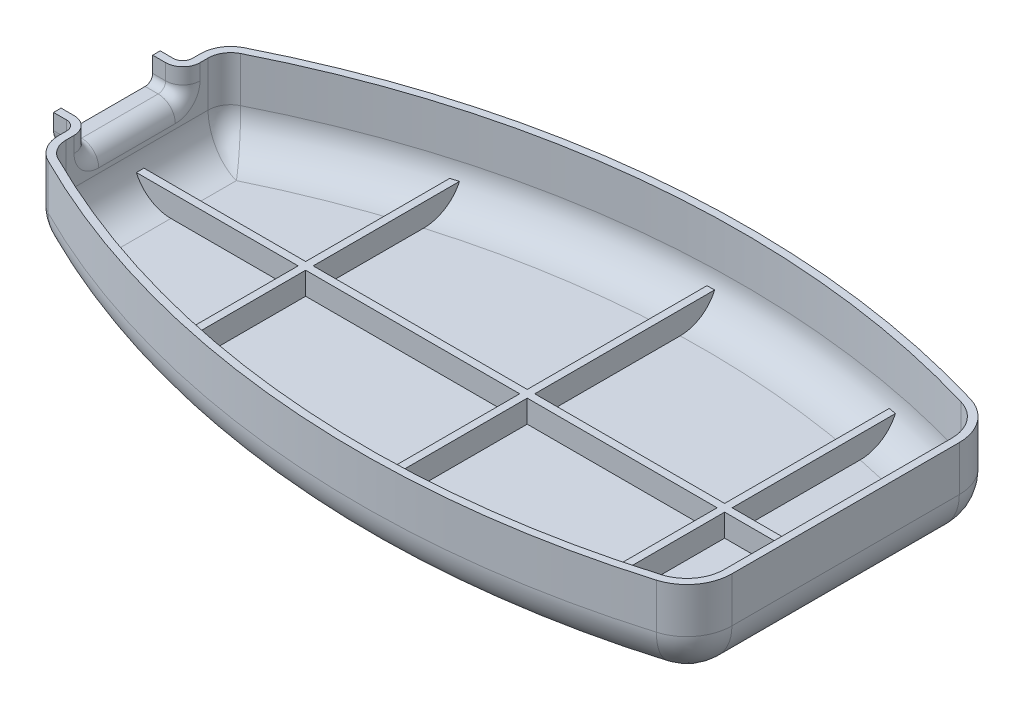
SolidWorks part; units mm, degrees
ref_plane "Front Plane" through (0, 0, 0) normal (0, 0, 1) x (1, 0, 0)
ref_plane "Top Plane" through (0, 0, 0) normal (0, 1, 0) x (1, 0, 0)
ref_plane "Right Plane" through (0, 0, 0) normal (1, 0, 0) x (0, 0, -1)
sketch "Sketch1" plane through (0, 0, 0) normal (0, 1, 0) x (1, 0, 0)
  line L0 (0, 0) -> (144.4846, 0) construction
  line L1 (151.1466, 23.9986) -> (151.1466, -23.9986)
  line L2 (151.1466, -30.9662) -> (151.3934, -31.9532)
  line L3 (0, 15.0032) -> (0, -15.0032)
  line L4 (0, -18.8758) -> (0.3867, -17.8889)
  arc A0 (3.5015, 20.6785) -> (144.3346, 33.1291) centre (89.6407, -150.9401) cw
  arc A1 (3.5015, -20.6785) -> (144.3346, -33.1291) centre (89.6407, 150.9401) ccw
  arc A2 (3.5015, -20.6785) -> (0, -15.0032) centre (6.35, -15.0032) cw
  arc A3 (3.5015, 20.6785) -> (0, 15.0032) centre (6.35, 15.0032) ccw
  arc A4 (144.3346, -33.1291) -> (151.1466, -23.9986) centre (141.6216, -23.9986) ccw
  arc A5 (144.3346, 33.1291) -> (151.1466, 23.9986) centre (141.6216, 23.9986) cw
  point P16 (0, 18.8758)
  point P22 (151.1466, 30.9662)
  dimension "D1" = 6.35
  dimension "D2" = 9.525
extrude "Boss-Extrude1" add sketch "Sketch1" against normal blind 19.05 contours A5 A0 A3 L3 A2 A1 A4 L1 region at (79.6386, 0, 0)
fillet "Fillet1" radius 9.525 8 edges at (0.9458, -19.05, 18.3375) (0, -19.05, 0) (0.9458, -19.05, -18.3375) (72.7305, -19.05, -40.337) (149.256, -19.05, -29.6944) (151.1466, -19.05, 0) (149.256, -19.05, 29.6944) (72.7305, -19.05, 40.337)
ref_plane "Plane1" through (-4.7752, 0, 0) normal (-1, 0, 0) x (0, 0, 1)
sketch "Sketch2" plane through (-4.7752, 0, 0) normal (-1, 0, 0) x (0, 0, 1)
  line L0 (0, 0) -> (0, -2.8991) construction
  line L1 (0, 0) -> (11.256, 0)
  line L2 (-15.0032, 0) -> (15.0032, 0) construction
  line L3 (-11.256, 0) -> (-11.256, -3.3329)
  line L4 (-8.081, -6.5079) -> (8.081, -6.5079)
  line L5 (11.256, 0) -> (11.256, -3.3329)
  line L8 (0, 0) -> (-11.256, 0)
  arc A0 (-11.256, -3.3329) -> (-8.081, -6.5079) centre (-8.081, -3.3329) ccw
  arc A1 (8.081, -6.5079) -> (11.256, -3.3329) centre (8.081, -3.3329) ccw
  dimension "D1" = 3.175
extrude "Boss-Extrude2" add sketch "Sketch2" against normal up to body
fillet "Fillet2" radius 2.032 5 edges at (0, -1.6664, -11.256) (0, -5.5779, -10.3261) (0, -6.5079, 0) (0, -5.5779, 10.3261) (0, -1.6664, 11.256)
shell "Shell1" thickness 1.5875 removed face at (-4.7752, -2.9995, 0) removed face at (33.8052, 0, 0)
ref_plane "Plane2" through (0, -12.7, 0) normal (0, 1, 0) x (-1, 0, 0)
sketch "Sketch3" plane through (0, -12.7, 0) normal (0, 1, 0) x (-1, 0, 0)
  line L0 (-9.525, 0) -> (-141.6216, 0)
  line L1 (-9.525, 13.0327) -> (-9.525, -13.0327) construction
  line L2 (-141.6216, -23.9986) -> (-141.6216, 23.9986) construction
  line L3 (-37.1794, 23.8552) -> (-37.1794, 6.3672)
  line L4 (-37.1794, -3.6768) -> (-37.1794, -21.6126)
  line L5 (-83.9418, 31.4691) -> (-83.9418, 6.3672)
  line L6 (-83.9418, -3.6768) -> (-83.9418, -26.9933)
  line L7 (-125.6119, 27.9779) -> (-125.6119, 3.8562)
  line L8 (-125.6119, -3.6768) -> (-125.6119, -24.1236)
  line L9 (-83.9418, 6.3672) -> (-83.9418, -3.6768) construction
  arc A0 (-9.525, 13.0327) -> (-141.6216, 23.9986) centre (-89.6407, -150.9401) ccw construction
  point P21 (-83.9418, 0)
rib "Rib1" sketch "Sketch3" sketch "Sketch3" thickness 1.5875 extrusion direction normal to sketch draft on no parameters "D1"=1.5875
ref_plane "Plane3" through (0, -25.4, 0) normal (0, 1, 0) x (-1, 0, 0)
sketch "Sketch4" plane through (0, -25.4, 0) normal (0, 1, 0) x (-1, 0, 0)
  point P0 (-83.9418, 0)
